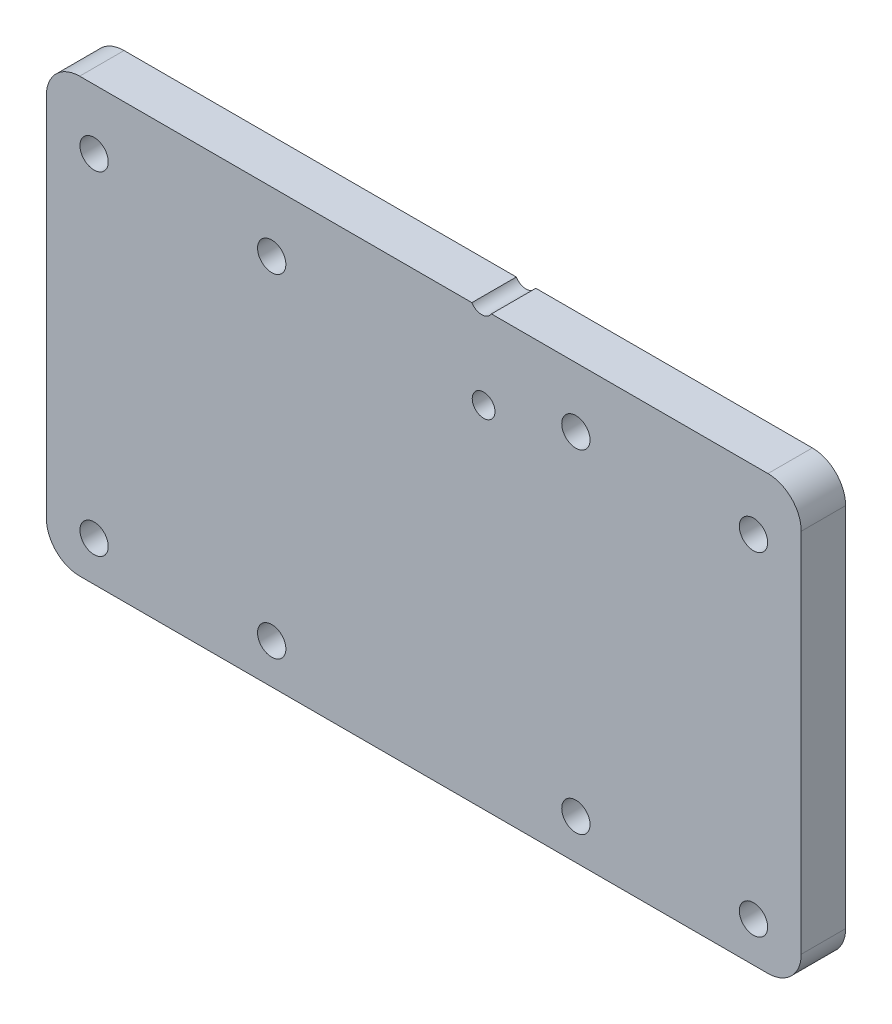
SolidWorks part; units mm, degrees
material "Thornel Mat VMA"
ref_plane "前视基准面" through (0, 0, 0) normal (0, 0, 1) x (1, 0, 0)
ref_plane "上视基准面" through (0, 0, 0) normal (0, 1, 0) x (1, 0, 0)
ref_plane "右视基准面" through (0, 0, 0) normal (1, 0, 0) x (0, 0, -1)
other "Configuration Table"
sketch "草图1" plane through (0, 0, 0) normal (0, 0, 1) x (1, 0, 0)
  line L1 (-34, -19.5) -> (34, -19.5)
  line L2 (-34, -19.5) -> (-34, 19.5)
  line L3 (-34, 19.5) -> (34, 19.5)
  line L4 (34, -19.5) -> (34, 19.5)
  line L5 (-34, -19.5) -> (34, 19.5) construction
  line L6 (-34, 19.5) -> (34, -19.5) construction
  point P0 (0, 0)
  dimension "D1" = 68
  dimension "D2" = 39
extrude "凸台-拉伸1" add sketch "草图1" along normal blind 4
sketch "草图2" plane through (0, 0, 0) normal (0, 0, -1) x (-1, 0, 0)
  arc A0 (29.7, -17.15) -> (29.7, -14.65) centre (29.7, -15.9) ccw construction
  arc A1 (29.7, 12.85) -> (29.7, 15.35) centre (29.7, 14.1) ccw construction
  arc A2 (13.7, 12.85) -> (13.7, 15.35) centre (13.7, 14.1) ccw construction
  arc A3 (13.7, -17.15) -> (13.7, -14.65) centre (13.7, -15.9) ccw construction
  arc A4 (-13.7, 12.85) -> (-13.7, 15.35) centre (-13.7, 14.1) ccw construction
  arc A5 (-29.7, 12.85) -> (-29.7, 15.35) centre (-29.7, 14.1) ccw construction
  arc A6 (-13.7, -17.15) -> (-13.7, -14.65) centre (-13.7, -15.9) ccw construction
  arc A7 (-29.7, -17.15) -> (-29.7, -14.65) centre (-29.7, -15.9) ccw construction
  arc A8 (29.7, -17.15) -> (29.7, -14.65) centre (29.7, -15.9) ccw construction
  arc A9 (29.7, 12.85) -> (29.7, 15.35) centre (29.7, 14.1) ccw construction
  arc A10 (13.7, 12.85) -> (13.7, 15.35) centre (13.7, 14.1) ccw construction
  arc A11 (13.7, -17.15) -> (13.7, -14.65) centre (13.7, -15.9) ccw construction
  arc A12 (-13.7, 12.85) -> (-13.7, 15.35) centre (-13.7, 14.1) ccw construction
  arc A13 (-29.7, 12.85) -> (-29.7, 15.35) centre (-29.7, 14.1) ccw construction
  arc A14 (-13.7, -17.15) -> (-13.7, -14.65) centre (-13.7, -15.9) ccw construction
  arc A15 (-29.7, -17.15) -> (-29.7, -14.65) centre (-29.7, -15.9) ccw construction
  circle A16 centre (29.7, 14.1) radius 1.275
  circle A17 centre (13.7, 14.1) radius 1.275
  circle A18 centre (13.7, -15.9) radius 1.275
  circle A19 centre (29.7, -15.9) radius 1.275
  circle A20 centre (-13.7, -15.9) radius 1.275
  circle A21 centre (-13.7, 14.1) radius 1.275
  circle A22 centre (-29.7, 14.1) radius 1.275
  circle A23 centre (-29.7, -15.9) radius 1.275
  dimension "D1" = 2.55
extrude "切除-拉伸1" cut sketch "草图2" against normal blind 51.4
sketch "草图3" plane through (0, 0, 0) normal (0, 0, -1) x (-1, 0, 0)
  circle A0 centre (-5.3871, 12.0292) radius 0.8 construction
  circle A1 centre (-5.2119, 20.0273) radius 0.8 construction
  circle A2 centre (-5.3871, 12.0292) radius 0.8 construction
  circle A3 centre (-5.2119, 20.0273) radius 0.8 construction
  circle A4 centre (-5.2119, 20.0273) radius 1.025
  circle A5 centre (-5.3871, 12.0292) radius 1.025
  dimension "D1" = 2.05
extrude "切除-拉伸2" cut sketch "草图3" against normal blind 81.4
fillet "圆角1" radius 3 4 edges at (34, -19.5, 2) (34, 19.5, 2) (-34, -19.5, 2) (-34, 19.5, 2)
